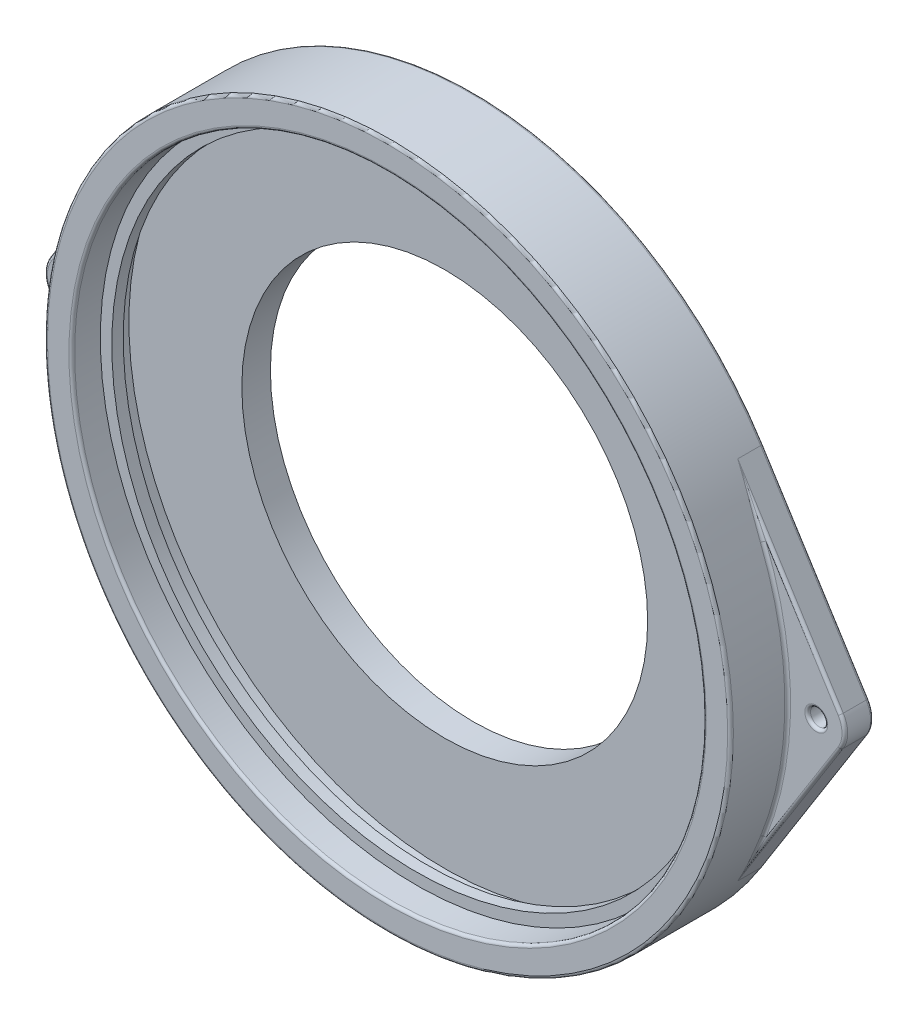
SolidWorks part; units mm, degrees
ref_plane "Plan de face" through (0, 0, 0) normal (0, 0, 1) x (1, 0, 0)
ref_plane "Plan de dessus" through (0, 0, 0) normal (0, 1, 0) x (1, 0, 0)
ref_plane "Plan de droite" through (0, 0, 0) normal (1, 0, 0) x (0, 0, -1)
sketch "Esquisse1" plane through (0, 0, 0) normal (0, 0, 1) x (1, 0, 0)
  circle A0 centre (0, 0) radius 60
  circle A1 centre (0, 0) radius 35.5
  dimension "D1" = 120
  dimension "D2" = 71
extrude "Boss.-Extru.1" add sketch "Esquisse1" along normal blind 5
sketch "Esquisse2" plane through (0, 0, 5) normal (0, 0, 1) x (1, 0, 0)
  circle A0 centre (0, 0) radius 55.25
  circle A2 centre (0, 0) radius 60
  circle A3 centre (0, 0) radius 60
  dimension "D1" = 110.5
  dimension "D2" = 0
extrude "Boss.-Extru.2" add sketch "Esquisse2" along normal blind 10
sketch "Esquisse3" plane through (0, 0, 0) normal (0, 0, -1) x (-1, 0, 0)
  line L0 (-109.1482, 0) -> (128.2491, 0) construction
  line L1 (0, 99.9009) -> (0, -92.018) construction
  line L2 (-69.2308, 2.6647) -> (-50.7692, 31.9763)
  line L3 (-69.2308, -2.6647) -> (-50.7692, -31.9763)
  line L4 (69.2308, -2.6647) -> (50.7692, -31.9763)
  line L5 (69.2308, 2.6647) -> (50.7692, 31.9763)
  arc A0 (-69.2308, 2.6647) -> (-69.2308, -2.6647) centre (-65, 0) ccw
  circle A1 centre (0, 0) radius 60 construction
  circle A2 centre (0, 0) radius 60
  circle A3 centre (-65, 0) radius 1.5
  circle A4 centre (65, 0) radius 1.5
  arc A5 (69.2308, 2.6647) -> (69.2308, -2.6647) centre (65, 0) cw
  circle M7 centre (0, 0) radius 60
  dimension "D1" = 10
  dimension "D2" = 3
extrude "Boss.-Extru.3" add sketch "Esquisse3" against normal blind 5 contours L2 A0 L3 A3 M7 | A5 L5 L4 A4 M7 region at (62.2599, 0, 0) region at (-62.2599, 0, 0)
fillet "Congé1" radius 0.5 20 edges at (-60, -17.3205, 0) (-70, 0, 0) (-60, 17.3205, 0) (60, 17.3205, 0) (70, 0, 0) (60, -17.3205, 0) (55.25, 0, 15) (70, 0, 5) (60, -17.3205, 5) (60, 17.3205, 5) (63.5, 0, 5) (-66.5, 0, 5) (-60, 17.3205, 5) (-60, -17.3205, 5) (-70, 0, 5) (60, 0, 15) (0, 60, 0) (60, 0, 5) (0, -60, 0) (-60, 0, 5)
sketch "Esquisse4" plane through (0, 0, 5) normal (0, 0, 1) x (1, 0, 0)
  circle A0 centre (0, 0) radius 53.25
  circle A1 centre (0, 0) radius 55.25
  circle A2 centre (0, 0) radius 55.25
  dimension "D1" = 0
  dimension "D2" = 2
extrude "Boss.-Extru.4" add sketch "Esquisse4" against normal blind 2 from offset 5
